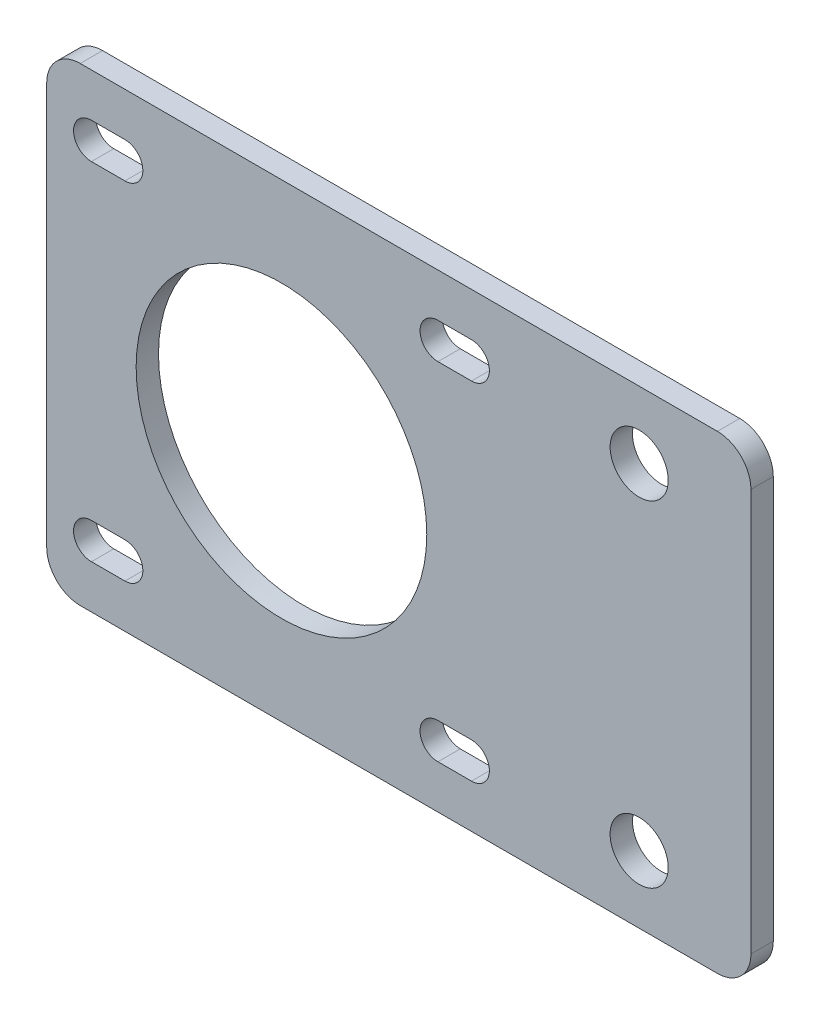
SolidWorks part; units mm, degrees
material "普通碳钢"
ref_plane "前视基准面" through (0, 0, 0) normal (0, 0, 1) x (1, 0, 0)
ref_plane "上视基准面" through (0, 0, 0) normal (0, 1, 0) x (1, 0, 0)
ref_plane "右视基准面" through (0, 0, 0) normal (1, 0, 0) x (0, 0, -1)
sketch "草图1" plane through (0, 0, 0) normal (0, 0, 1) x (1, 0, 0)
  line L0 (0, 0) -> (19581.1258, 0) construction
  line L1 (0, 0) -> (0, 19581.1258) construction
  line L2 (42, 18) -> (42, -18)
  line L3 (39, -21) -> (-18, -21)
  line L4 (-21, -18) -> (-21, 18)
  line L5 (-18, 21) -> (39, 21)
  line L6 (-14, 15.5) -> (-17, 15.5) construction
  line L7 (-14, 13.9) -> (-17, 13.9)
  line L8 (-14, 17.1) -> (-17, 17.1)
  line L9 (-14, -15.5) -> (-17, -15.5) construction
  line L10 (-14, -17.1) -> (-17, -17.1)
  line L11 (-14, -13.9) -> (-17, -13.9)
  line L12 (17, 15.5) -> (14, 15.5) construction
  line L13 (17, 13.9) -> (14, 13.9)
  line L14 (17, 17.1) -> (14, 17.1)
  line L15 (17, -15.5) -> (14, -15.5) construction
  line L16 (17, -17.1) -> (14, -17.1)
  line L17 (17, -13.9) -> (14, -13.9)
  circle A0 centre (0, 0) radius 13
  arc A1 (-14, 13.9) -> (-14, 17.1) centre (-14, 15.5) ccw
  arc A2 (-17, 17.1) -> (-17, 13.9) centre (-17, 15.5) ccw
  arc A3 (-14, -17.1) -> (-14, -13.9) centre (-14, -15.5) ccw
  arc A4 (-17, -13.9) -> (-17, -17.1) centre (-17, -15.5) ccw
  circle A5 centre (32, 15) radius 2.6
  circle A6 centre (32, -15) radius 2.6
  arc A7 (42, 18) -> (39, 21) centre (39, 18) ccw
  arc A8 (-18, 21) -> (-21, 18) centre (-18, 18) ccw
  arc A9 (-21, -18) -> (-18, -21) centre (-18, -18) ccw
  arc A10 (39, -21) -> (42, -18) centre (39, -18) ccw
  arc A11 (17, 13.9) -> (17, 17.1) centre (17, 15.5) ccw
  arc A12 (14, 17.1) -> (14, 13.9) centre (14, 15.5) ccw
  arc A13 (17, -17.1) -> (17, -13.9) centre (17, -15.5) ccw
  arc A14 (14, -13.9) -> (14, -17.1) centre (14, -15.5) ccw
  point P13 (-15.5, 15.5)
  point P21 (-15.5, -15.5)
  point P38 (15.5, 15.5)
  point P45 (15.5, -15.5)
  dimension "D1" = 26
  dimension "D5" = 31
  dimension "D10" = 5.2
  dimension "D11" = 3
  dimension "D3" = 1.6
  dimension "D2" = 42
  dimension "D4" = 3
  dimension "D6" = 21
  dimension "D7" = 42
  dimension "D8" = 30
  dimension "D9" = 10
  dimension "D12" = 31
base flange "基体-法兰1" sketch "草图1" thickness 2 reverse thickness direction no parameters "D1"=2
sketch "折弯-线1" [suppressed] plane through (0, 0, 0) normal (0, 1, 0) x (1, 0, 0)
sketch "边界框1" [suppressed] plane through (0, 0, 0) normal (0, 1, 0) x (1, 0, 0)
sheet metal parameters "钣金6" thickness 2 parameters "D1"=2
flat pattern "平板型式6" [suppressed]
sketch "折弯-线2" plane through (0, 0, 0) normal (0, 1, 0) x (1, 0, 0)
sketch3d "边界框2" [suppressed]
  line L0 (-60, 3, 0) -> (3, 3, 0) construction
  line L1 (-60, -39, 0) -> (3, -39, 0) construction
  line L2 (-60, 3, 0) -> (-60, -39, 0) construction
  line L3 (3, 3, 0) -> (3, -39, 0) construction
